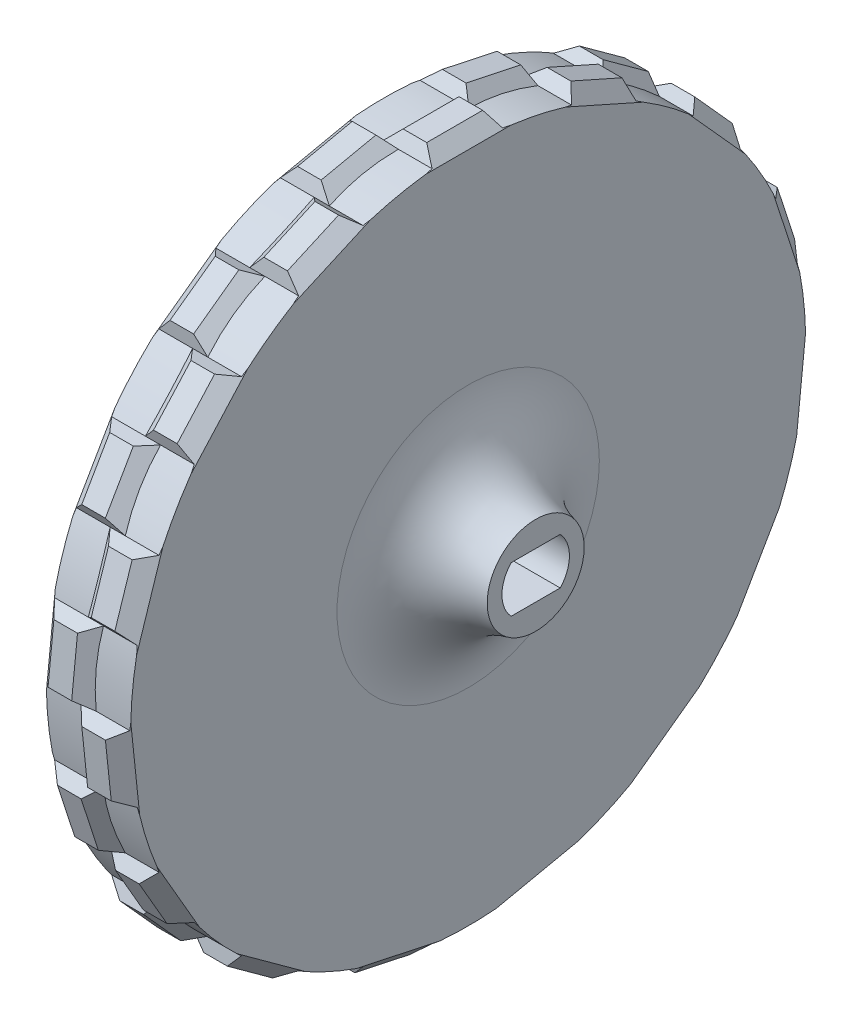
SolidWorks part; units mm, degrees
ref_plane "Front Plane" through (0, 0, 0) normal (0, 0, 1) x (1, 0, 0)
ref_plane "Top Plane" through (0, 0, 0) normal (0, 1, 0) x (1, 0, 0)
ref_plane "Right Plane" through (0, 0, 0) normal (1, 0, 0) x (0, 0, -1)
sketch "Sketch1" plane through (0, 0, 0) normal (1, 0, 0) x (0, 0, -1)
  circle A0 centre (0, 0) radius 40
  dimension "D1" = 80
extrude "Boss-Extrude1" add sketch "Sketch1" along normal blind 10
sketch "Sketch2" plane through (10, 0, 0) normal (1, 0, 0) x (0, 0, -1)
  line L0 (-4.1811, 39.7809) -> (-3.3151, 41.2809)
  line L1 (-3.3151, 41.2809) -> (3.3151, 41.2809)
  line L2 (3.3151, 41.2809) -> (4.1811, 39.7809)
  line L3 (4.1811, 39.7809) -> (-4.1811, 39.7809)
  line L4 (-4.1811, 39.7809) -> (0, 0) construction
  line L5 (0, 0) -> (4.1811, 39.7809) construction
  circle A0 centre (0, 0) radius 40 construction
  point P4 (0, 39.7809)
  dimension "D1" = 60
  dimension "D2" = 60
  dimension "D4" = 1.5
  dimension "D3" = 12
extrude "Boss-Extrude2" add sketch "Sketch2" against normal blind 6
chamfer "Chamfer1" distance 1.6 angle 45 2 edges at (10, 41.2809, 0) (4, 41.2809, 0)
pattern_circular "CirPattern1" count 15 over 360 about axis through (10, 0, 0) along (1, 0, 0) of "Boss-Extrude2", "Chamfer1"
sketch "Sketch4" plane through (0, 0, 0) normal (-1, 0, 0) x (0, 0, 1)
  line L0 (0, 40) -> (0, 0) construction
  line L1 (0, 0) -> (-8.3165, 39.1259) construction
  line L6 (-12.3607, 38.0423) -> (-4.1811, 39.7809)
  line L7 (-4.1811, 39.7809) -> (-5.3401, 41.068)
  line L8 (-5.3401, 41.068) -> (-11.8254, 39.6895)
  line L9 (-11.8254, 39.6895) -> (-12.3607, 38.0423)
  line L10 (-12.3607, 38.0423) -> (0, 0) construction
  line L11 (0, 0) -> (-4.1811, 39.7809) construction
  circle A1 centre (0, 0) radius 40 construction
  point P13 (-8.2709, 38.9116)
  dimension "D2" = 60
  dimension "D1" = 12
  dimension "D3" = 60
  dimension "D4" = 12
  dimension "D5" = 1.5
extrude "Boss-Extrude3" add sketch "Sketch4" against normal blind 6
chamfer "Chamfer2" distance 1.6 angle 45 2 edges at (6, 40.3788, -8.5828) (0, 40.3788, -8.5828)
pattern_circular "CirPattern2" count 15 over 360 about axis through (0, 0, 0) along (1, 0, 0) of "Boss-Extrude3", "Chamfer2"
sketch "Sketch5" plane through (10, 0, 0) normal (1, 0, 0) x (0, 0, -1)
  circle A0 centre (0, 0) radius 5.75
  dimension "D1" = 11.5
extrude "Boss-Extrude4" add sketch "Sketch5" along normal blind 8
sketch "Sketch6" plane through (18, 0, 0) normal (1, 0, 0) x (0, 0, -1)
  line L0 (-2.9047, 2.75) -> (2.9047, 2.75)
  line L1 (2.9047, -2.75) -> (-2.9047, -2.75)
  circle A0 centre (0, 0) radius 4
  dimension "D1" = 8
  dimension "D2" = 5.5
extrude "Cut-Extrude1" cut sketch "Sketch6" against normal blind 6.1 contours L0 A0 L1 region at (18, 0, 0)
fillet "Fillet1" radius 10 1 edges at (10, 0, -5.75)
sketch "Sketch7" plane through (18, 0, 0) normal (1, 0, 0) x (0, 0, -1)
  circle A0 centre (0, 0) radius 5.914
  circle A1 centre (0, 0) radius 59.3048
equation "\"D2@Sketch2\"=\"D1@Sketch2\""
equation "\"D3@Sketch4\"=\"D2@Sketch4\""
equation "\"Num Treads\"= 15"
equation "\"D1@CirPattern1\"=\"Num Treads\""
equation "\"D1@CirPattern2\"=\"Num Treads\""
